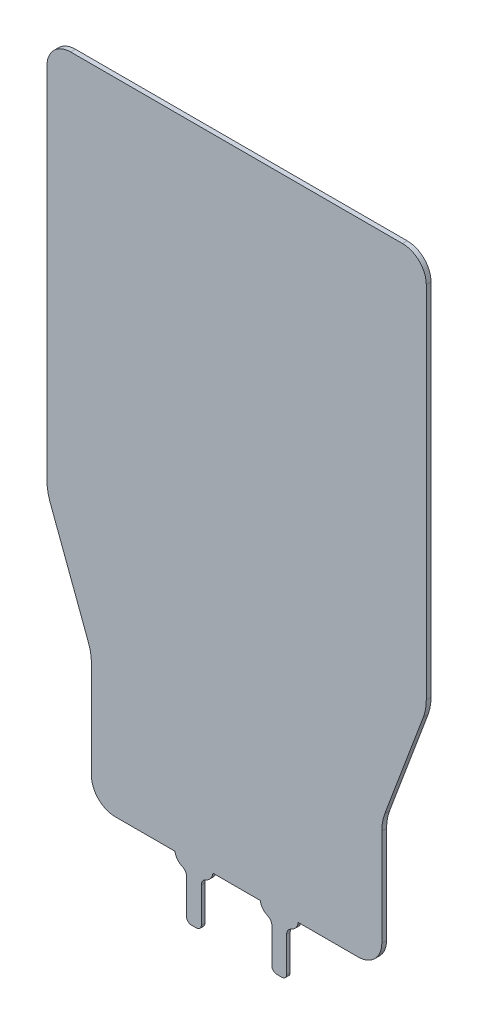
SolidWorks part; units mm, degrees
material "Alloy Steel"
ref_plane "Front Plane" through (0, 0, 0) normal (0, 0, 1) x (1, 0, 0)
ref_plane "Top Plane" through (0, 0, 0) normal (0, 1, 0) x (1, 0, 0)
ref_plane "Right Plane" through (0, 0, 0) normal (1, 0, 0) x (0, 0, -1)
sketch "Sketch2" plane through (0, 0, 0) normal (0, 0, 1) x (1, 0, 0)
  line L1 (-5.1238, -13.5) -> (5.1238, -13.5)
  line L2 (-8, -2.6704) -> (-8, 12.5)
  line L3 (-7, 13.5) -> (7, 13.5)
  line L4 (8, -2.6704) -> (8, 12.5)
  line L8 (-6.1238, -12.5) -> (-6.1238, -8.3989)
  line L10 (6.1238, -12.5) -> (6.1238, -8.3989)
  line L11 (7.8727, -3.3727) -> (6.2512, -7.6966)
  line L12 (-6.2512, -7.6966) -> (-7.8727, -3.3727)
  circle A0 centre (0, 5.6597) radius 5 construction
  circle A1 centre (0, 5.6597) radius 6.2 construction
  arc A2 (6.1238, -12.5) -> (5.1238, -13.5) centre (5.1238, -12.5) cw
  arc A3 (-5.1238, -13.5) -> (-6.1238, -12.5) centre (-5.1238, -12.5) cw
  arc A4 (7, 13.5) -> (8, 12.5) centre (7, 12.5) cw
  arc A5 (-8, 12.5) -> (-7, 13.5) centre (-7, 12.5) cw
  arc A6 (-6.1238, -8.3989) -> (-6.2512, -7.6966) centre (-8.1238, -8.3989) ccw
  arc A7 (6.2512, -7.6966) -> (6.1238, -8.3989) centre (8.1238, -8.3989) ccw
  arc A8 (8, -2.6704) -> (7.8727, -3.3727) centre (6, -2.6704) cw
  arc A9 (-8, -2.6704) -> (-7.8727, -3.3727) centre (-6, -2.6704) ccw
  point P0 (0, 0)
  point P6 (0, -13.5)
  point P13 (0, 4.9093)
  point P15 (0, 5.6597)
  point P22 (8, 13.5)
  point P25 (-8, 13.5)
  dimension "D3" = 10
  dimension "D4" = 12.4
  dimension "D5" = 1
  dimension "D6" = 2
  dimension "D1" = 16
  dimension "D2" = 27
extrude "Boss-Extrude1" add sketch "Sketch2" along normal blind 0.2
sketch "Sketch3" plane through (0, 0, 0) normal (0, 0, -1) x (-1, 0, 0)
  line L0 (0, 0.11) -> (0, -0.11) construction
  line L2 (1, 0.0983) -> (1, -13.8753)
  line L3 (1, -13.8753) -> (1.1893, -13.8753)
  line L4 (2.6, 0.5886) -> (2.6, -13.8753)
  line L5 (-2.6, 0.5886) -> (-2.6, -13.8753)
  line L6 (-1, -13.8753) -> (-1.1893, -13.8753)
  line L7 (-1, 0.0983) -> (-1, -13.8753)
  line L8 (2.4107, -13.8753) -> (2.6, -13.8753)
  line L9 (1.4893, -15.8504) -> (2.1107, -15.8504)
  line L10 (1.4893, -15.8504) -> (1.4893, -14.1753)
  line L12 (2.1107, -15.8504) -> (2.1107, -14.1753)
  line L13 (-1.4893, -15.8504) -> (-2.1107, -15.8504)
  line L14 (-1.4893, -15.8504) -> (-1.4893, -14.1753)
  line L15 (-2.1107, -15.8504) -> (-2.1107, -14.1753)
  line L16 (-2.4107, -13.8753) -> (-2.6, -13.8753)
  circle A0 centre (0, 6.2171) radius 5
  arc A1 (-1, 0.0983) -> (1, 0.0983) centre (0, 6.2171) ccw
  arc A2 (2.6, 0.5886) -> (-2.6, 0.5886) centre (0, 6.2171) ccw
  arc A3 (1.4893, -14.1753) -> (1.1893, -13.8753) centre (1.1893, -14.1753) ccw
  arc A4 (2.1107, -14.1753) -> (2.4107, -13.8753) centre (2.4107, -14.1753) cw
  arc A5 (-2.1107, -14.1753) -> (-2.4107, -13.8753) centre (-2.4107, -14.1753) ccw
  arc A6 (-1.4893, -14.1753) -> (-1.1893, -13.8753) centre (-1.1893, -14.1753) cw
  point P2 (1.8, -13.8753)
  point P22 (2.1107, -13.8753)
  dimension "D1" = 10
  dimension "D2" = 0.3
  dimension "D3" = 1.6
  dimension "D4" = 1
extrude "Boss-Extrude2" add sketch "Sketch3" against normal blind 0.2
sketch "Sketch4" plane through (0, 0, 0) normal (0, 0, -1) x (-1, 0, 0)
  line L14 (1, -13.8753) -> (1.1893, -13.8753)
  line L15 (1, 0.0983) -> (1, -13.8753)
  line L16 (-1, -13.8753) -> (-1, 0.0983)
  line L17 (-1.1893, -13.8753) -> (-1, -13.8753)
  line L18 (-1.4893, -15.8504) -> (-1.4893, -14.1753)
  line L19 (-2.1107, -15.8504) -> (-1.4893, -15.8504)
  line L20 (-2.1107, -14.1753) -> (-2.1107, -15.8504)
  line L21 (-2.6, -13.8753) -> (-2.4107, -13.8753)
  line L22 (-2.6, 0.5886) -> (-2.6, -13.8753)
  line L23 (2.6, -13.8753) -> (2.6, 0.5886)
  line L24 (2.4107, -13.8753) -> (2.6, -13.8753)
  line L25 (2.1107, -15.8504) -> (2.1107, -14.1753)
  line L26 (1.4893, -15.8504) -> (2.1107, -15.8504)
  line L27 (1.4893, -14.1753) -> (1.4893, -15.8504)
  line L28 (1, -13.8753) -> (1.1893, -13.8753)
  line L29 (1, 0.0983) -> (1, -13.8753)
  line L30 (-1, -13.8753) -> (-1, 0.0983)
  line L31 (-1.1893, -13.8753) -> (-1, -13.8753)
  line L32 (-1.4893, -15.8504) -> (-1.4893, -14.1753)
  line L33 (-2.1107, -15.8504) -> (-1.4893, -15.8504)
  line L34 (-2.1107, -14.1753) -> (-2.1107, -15.8504)
  line L35 (-2.6, -13.8753) -> (-2.4107, -13.8753)
  line L36 (-2.6, 0.5886) -> (-2.6, -13.8753)
  line L37 (2.6, -13.8753) -> (2.6, 0.5886)
  line L38 (2.4107, -13.8753) -> (2.6, -13.8753)
  line L39 (2.1107, -15.8504) -> (2.1107, -14.1753)
  line L40 (1.4893, -15.8504) -> (2.1107, -15.8504)
  line L41 (1.4893, -14.1753) -> (1.4893, -15.8504)
  circle A1 centre (0, 6.2171) radius 5
  circle A2 centre (0, 6.2171) radius 5
  arc A8 (-1, 0.0983) -> (1, 0.0983) centre (0, 6.2171) ccw
  arc A9 (-1.1893, -13.8753) -> (-1.4893, -14.1753) centre (-1.1893, -14.1753) ccw
  arc A10 (-2.1107, -14.1753) -> (-2.4107, -13.8753) centre (-2.4107, -14.1753) ccw
  arc A11 (2.6, 0.5886) -> (-2.6, 0.5886) centre (0, 6.2171) ccw
  arc A12 (2.4107, -13.8753) -> (2.1107, -14.1753) centre (2.4107, -14.1753) ccw
  arc A13 (1.4893, -14.1753) -> (1.1893, -13.8753) centre (1.1893, -14.1753) ccw
  arc A14 (-1, 0.0983) -> (1, 0.0983) centre (0, 6.2171) ccw
  arc A15 (-1.1893, -13.8753) -> (-1.4893, -14.1753) centre (-1.1893, -14.1753) ccw
  arc A16 (-2.1107, -14.1753) -> (-2.4107, -13.8753) centre (-2.4107, -14.1753) ccw
  arc A17 (2.6, 0.5886) -> (-2.6, 0.5886) centre (0, 6.2171) ccw
  arc A18 (2.4107, -13.8753) -> (2.1107, -14.1753) centre (2.4107, -14.1753) ccw
  arc A19 (1.4893, -14.1753) -> (1.1893, -13.8753) centre (1.1893, -14.1753) ccw
  dimension "D1" = 0
  dimension "D2" = 0
extrude "Cut-Extrude1" cut sketch "Sketch4" against normal blind 0.05
fillet "Fillet1" radius 0.5 4 edges at (-2.6, -13.8753, 0.125) (-1, -13.8753, 0.125) (1, -13.8753, 0.125) (2.6, -13.8753, 0.125)
fillet "Fillet2" radius 0.2 4 edges at (-2.1107, -15.8504, 0.125) (-1.4893, -15.8504, 0.125) (1.4893, -15.8504, 0.125) (2.1107, -15.8504, 0.125)
